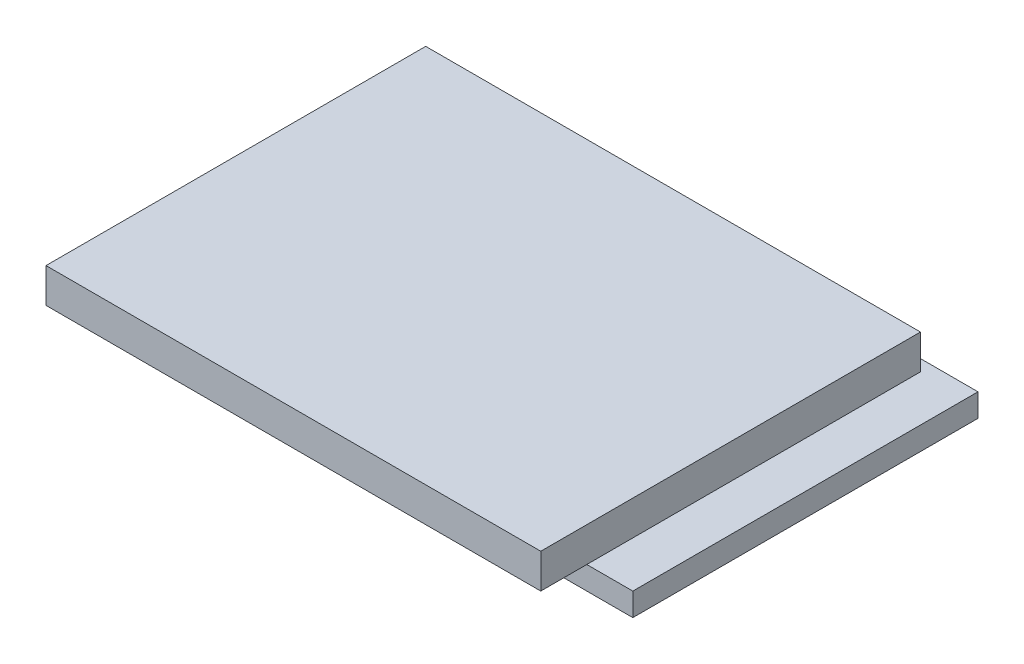
SolidWorks part; units mm, degrees
ref_plane "Front Plane" through (0, 0, 0) normal (0, 0, 1) x (1, 0, 0)
ref_plane "Top Plane" through (0, 0, 0) normal (0, 1, 0) x (1, 0, 0)
ref_plane "Right Plane" through (0, 0, 0) normal (1, 0, 0) x (0, 0, -1)
sketch "Sketch1" plane through (0, 0, 0) normal (0, 1, 0) x (1, 0, 0)
  line L1 (0, 0) -> (48, 0)
  line L2 (0, 0) -> (0, -30)
  line L3 (0, -30) -> (48, -30)
  line L4 (48, 0) -> (48, -30)
  dimension "D1" = 48
  dimension "D2" = 30
extrude "Boss-Extrude1" add sketch "Sketch1" along normal blind 2
sketch "Sketch2" plane through (0, 2, 0) normal (0, 1, 0) x (1, 0, 0)
  line L0 (48, 0) -> (0, 0) construction
  line L1 (1, -1) -> (44, -1)
  line L2 (1, -1) -> (1, -34)
  line L3 (1, -34) -> (44, -34)
  line L4 (44, -1) -> (44, -34)
  line L5 (0, 0) -> (0, -30) construction
  dimension "D1" = 43
  dimension "D2" = 33
  dimension "D3" = 1
  dimension "D4" = 1
extrude "Boss-Extrude2" add sketch "Sketch2" along normal blind 3
sketch "Sketch3" plane through (0, 0, 0) normal (0, -1, 0) x (1, 0, 0)
  line L0 (0, 30) -> (48, 30) construction
  line L1 (25.0892, 15) -> (30.5804, 15)
  line L2 (25.0892, 15) -> (25.0892, 12)
  line L3 (25.0892, 12) -> (30.5804, 12)
  line L4 (30.5804, 15) -> (30.5804, 12)
  dimension "D1" = 15
  dimension "D2" = 3
extrude "Boss-Extrude3" add sketch "Sketch3" along normal blind 5
sketch "Sketch4" plane through (0, 0, 15) normal (0, 0, 1) x (1, 0, 0)
  circle A0 centre (27.5602, -2.6198) radius 1
  dimension "D1" = 2
extrude "Cut-Extrude1" cut sketch "Sketch4" against normal through all
